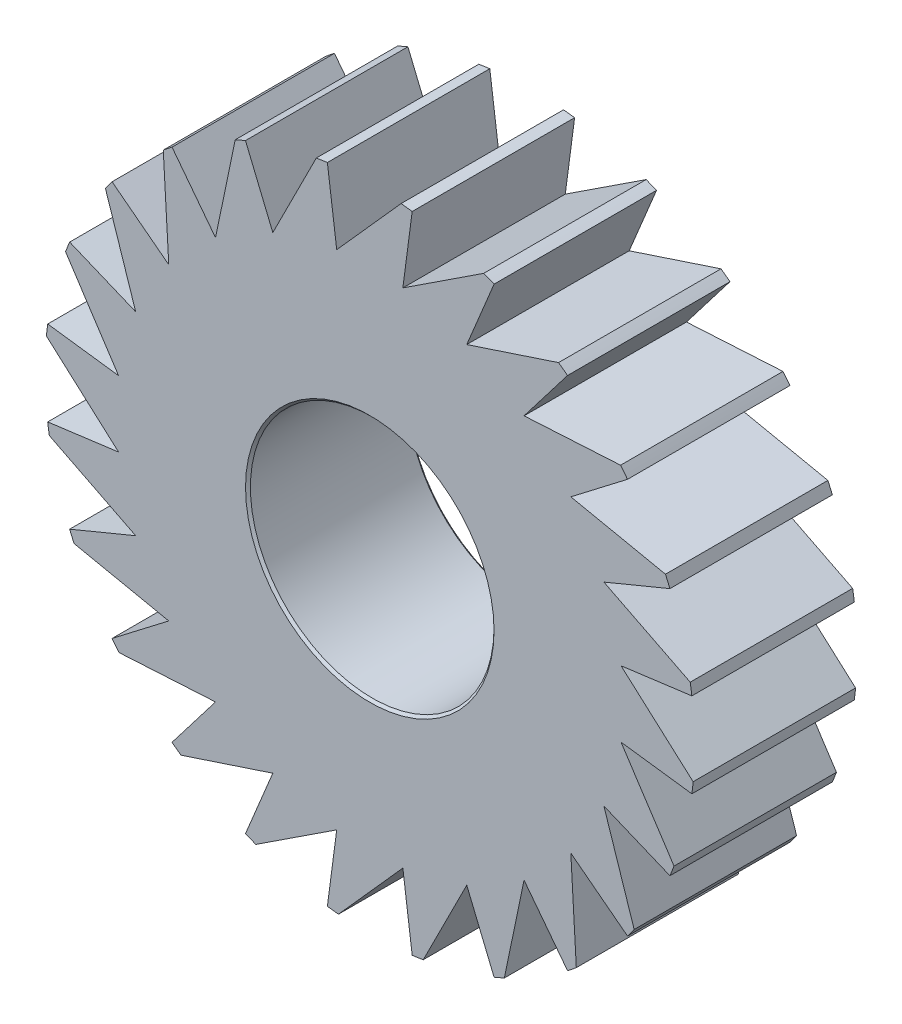
SolidWorks part; units mm, degrees
material "6061-T6 (SS)"
ref_plane "Front" through (0, 0, 0) normal (0, 0, 1) x (1, 0, 0)
ref_plane "Top" through (0, 0, 0) normal (0, 1, 0) x (1, 0, 0)
ref_plane "Right" through (0, 0, 0) normal (1, 0, 0) x (0, 0, -1)
sketch "Sketch1" plane through (0, 0, 0) normal (0, 0, 1) x (1, 0, 0)
  line L0 (-304.8, 0) -> (304.8, 0) construction
  circle A0 centre (0, 0) radius 12.7 construction
  circle A1 centre (0, 0) radius 13.335 construction
  circle A2 centre (0, 0) radius 4.7625
  circle A3 centre (0, 0) radius 9.906
  point P8 (0, 12.7)
  point P9 (0, -12.7)
  dimension "D1" = 19.812
  dimension "D2" = 26.67
extrude "Boss-Extrude1" add sketch "Sketch1" against normal blind 6.35
sketch "Sketch2" plane through (0, 0, 0) normal (0, 0, 1) x (1, 0, 0)
  line L0 (0, 0) -> (0, 12.7) construction
  line L1 (0, 0) -> (-1.293, 9.8213) construction
  line L2 (0, 0) -> (1.7406, 13.2209) construction
  line L3 (-1.293, 9.8213) -> (1.293, 9.8213) construction
  line L4 (-1.293, 9.8213) -> (1.7406, 13.2209)
  line L5 (1.7406, 13.2209) -> (1.293, 9.8213)
  circle A0 centre (0, 0) radius 12.7 construction
  circle A1 centre (0, 0) radius 13.335 construction
  circle A2 centre (0, 0) radius 9.906 construction
  arc A4 (1.293, 9.8213) -> (-1.293, 9.8213) centre (0, 0) ccw
  point P11 (0, 9.8213)
  dimension "D1" = 15
extrude "Boss-Extrude2" add sketch "Sketch2" against normal blind 6.35
pattern_circular "CirPattern1" count 24 over 360 about axis through (0, 0, -6.35) along (0, 0, 1) of "Boss-Extrude2"
chamfer "Chamfer1" distance 0.0953 angle 45 2 edges at (4.7625, 0, -6.35) (4.7625, 0, 0)
sketch "Pawl" plane through (0, 0, 0) normal (0, 0, 1) x (1, 0, 0)
  line L0 (1.6577, 12.5913) -> (4.4531, 11.8937) construction
  line L1 (1.293, 9.8213) -> (1.7406, 13.2209) construction
  line L2 (5.1031, 12.3199) -> (1.293, 9.8213) construction
  circle A0 centre (0, 0) radius 12.7 construction
  point P4 (3.0554, 12.2425)
  line B0 (3.0554, 13.0045) -> (3.0554, 12.2425)
  circle B1 centre (19.7242, 13.0363) radius 1.1906
  arc B2 (19.0678, 10.7473) -> (19.7242, 15.4175) centre (19.7242, 13.0363) ccw
  arc B3 (8.0376, 15.4175) -> (3.0554, 13.0045) centre (8.0376, 9.0675) ccw
  arc B4 (10.6187, 13.17) -> (3.8174, 12.2425) centre (7.9399, 7.4127) ccw
sketch_block_instance "Block1-1"
sketch_block "Block1"
sketch "Ref" plane through (0, 0, 0) normal (1, 0, 0) x (0, 0, -1)
  line L0 (0.0952, 4.7625) -> (6.2548, 4.7625) construction
  line L1 (6.2548, 4.7625) -> (6.35, 4.8578) construction
  line L2 (0.0952, 4.7625) -> (0, 4.8577) construction
  line L3 (0, -5.9543) -> (0.0952, -4.7625) construction
  line L4 (0, -8.1178) -> (0, -3.7909) construction
  line L5 (0.0952, -4.7625) -> (6.2548, -4.7625) construction
  line L6 (6.2548, -4.7625) -> (6.35, -4.8578) construction
sketch "Sketch3" plane through (0, 0, 0) normal (0, 0, 1) x (1, 0, 0)
  circle A0 centre (0, 0) radius 12.7 construction
  circle A1 centre (0, 0) radius 12.7
extrude "Cut-Extrude-Thin1" cut sketch "Sketch3" against normal through all flip side to cut thin thin type one direction wall 304.8
equation "\"D1@Sketch2\" = 360/\"Teeth@Sketch1\""
equation "\"D1@Boss-Extrude2\" = \"D1@Boss-Extrude1\""
equation "\"D1@CirPattern1\" = \"Teeth@Sketch1\""
equation "\"D1@Chamfer1\" = \"Bore Dia.@Sketch1\"*.01"
equation "\"D1@Sketch1\"=\"OD@Sketch1\"-.22"
equation "\"D2@Sketch1\"=\"OD@Sketch1\"+.05"
